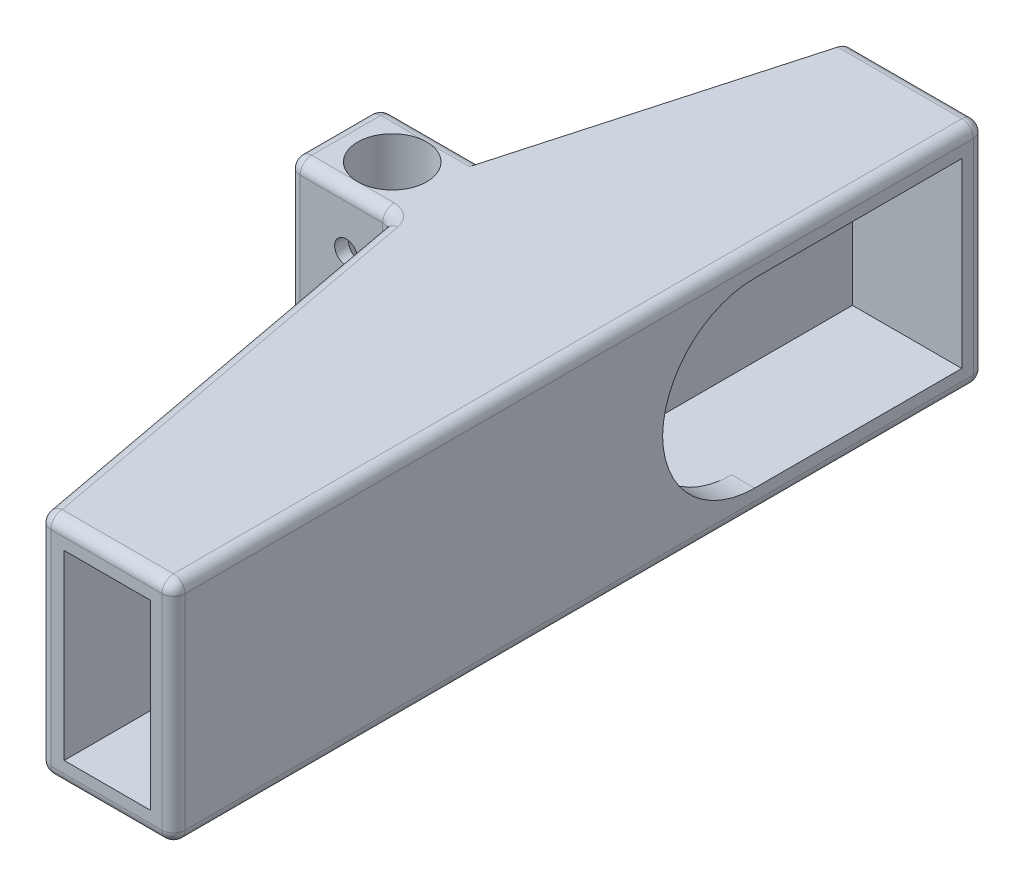
SolidWorks part; units mm, degrees
ref_plane "Alzado" through (0, 0, 0) normal (1, 0, 0) x (0, 1, 0)
ref_plane "Planta" through (0, 0, 0) normal (0, 0, 1) x (0, 1, 0)
ref_plane "Vista lateral" through (0, 0, 0) normal (0, 1, 0) x (-1, 0, 0)
sketch "Croquis1" plane through (0, 0, 0) normal (0, 0, 1) x (0, 1, 0)
  line L1 (-9.9, -5.75) -> (9.9, -5.75)
  line L2 (-9.9, -5.75) -> (-9.9, 5.75)
  line L3 (-9.9, 5.75) -> (9.9, 5.75)
  line L4 (9.9, -5.75) -> (9.9, 5.75)
  line L5 (-9.9, -5.75) -> (9.9, 5.75) construction
  line L6 (-9.9, 5.75) -> (9.9, -5.75) construction
  point P0 (0, 0)
  dimension "D1" = 19.8
  dimension "D2" = 11.5
extrude "Saliente-Extruir1" add sketch "Croquis1" along normal blind 70.5 contours L2 L1 L4 L3
shell "Vaciado1" thickness 2 removed face at (0, 0, 70.5)
sketch "Croquis4" plane through (5.75, 0, 0) normal (1, 0, 0) x (0, 1, 0)
sketch "Croquis5" plane through (5.75, 0, 0) normal (1, 0, 0) x (0, 1, 0)
  line L0 (-7.9, 70.5) -> (-7.9, 68.5)
  line L1 (-7.9, 70.5) -> (7.9, 70.5)
  line L2 (-7.9, 68.5) -> (7.9, 68.5)
  line L3 (7.9, 70.5) -> (7.9, 68.5)
  line L5 (-9.9, 70.5) -> (9.9, 70.5) construction
  point P0 (0, 0)
  dimension "D1" = 15.8
  dimension "D2" = 2
extrude "Saliente-Extruir2" add sketch "Croquis5" against normal blind 2 contours L0 L1 L3 L2
sketch "Croquis6" plane through (-5.75, 0, 0) normal (-1, 0, 0) x (0, -1, 0)
  line L0 (-9.9, 25) -> (9.9, 25)
  line L1 (-9.9, 25) -> (-9.9, 33)
  line L2 (9.9, 25) -> (9.9, 33)
  line L3 (-9.9, 33) -> (9.9, 33)
  line L4 (9.9, 0) -> (-9.9, 0) construction
  line L5 (-9.9, 70.5) -> (-9.9, 0) construction
  line L6 (9.9, 70.5) -> (9.9, 0) construction
  dimension "D1" = 8
  dimension "D2" = 25
extrude "Saliente-Extruir4" add sketch "Croquis6" along normal blind 16
sketch "Croquis9" plane through (0, -9.9, 0) normal (0, -1, 0) x (1, 0, 0)
  line L0 (-5.75, 70.5) -> (-12.75, 33)
  line L1 (-21.75, 33) -> (-5.75, 33) construction
  line L2 (-12.75, 33) -> (-5.75, 33)
  line L3 (-5.75, 33) -> (-5.75, 70.5)
  line L4 (-5.75, 0) -> (-12.75, 25)
  line L5 (-21.75, 25) -> (-5.75, 25) construction
  line L6 (-12.75, 25) -> (-5.75, 25)
  line L7 (-5.75, 25) -> (-5.75, 0) construction
  line L8 (-5.75, 25) -> (-5.75, 0)
  dimension "D1" = 7
  dimension "D2" = 7
extrude "Saliente-Extruir5" add sketch "Croquis9" against normal blind 19.8
sketch "Croquis10" plane through (0, -9.9, 0) normal (0, -1, 0) x (1, 0, 0)
  line L0 (-21.75, 25) -> (-21.75, 33) construction
  circle A0 centre (-16.7453, 29) radius 3
  point P4 (-21.75, 29)
  dimension "D1" = 6
  dimension "D2" = 5.0047
extrude "Cortar-Extruir4" cut sketch "Croquis10" against normal blind 19.8
sketch "Croquis8" plane through (-4, 0, 33) normal (0, 0, 1) x (1, 0, 0)
  line L0 (-17.75, -9.9) -> (-8.75, -9.9) construction
  line L1 (-17.75, -9.9) -> (-17.75, 9.9) construction
  circle A0 centre (-12.75, 5.1) radius 1
  circle A1 centre (-12.75, -4.9) radius 1
  point P0 (0, 0)
  dimension "D4" = 2
  dimension "D5" = 2
  dimension "D1" = 10
  dimension "D2" = 5
  dimension "D3" = 5
extrude "Cortar-Extruir3" cut sketch "Croquis8" against normal through all both and the other way through all contours A0 | A1 | A0 region at (-16.75, 5.1, 33)
sketch "Croquis11" plane through (5.75, 0, 0) normal (1, 0, 0) x (0, 1, 0)
  line L2 (-7.9, 2) -> (7.9, 2)
  line L6 (7.9, 2) -> (7.9, 28)
  line L7 (-7.9, 2) -> (-7.9, 28)
  line L8 (-7.9, 28) -> (7.9, 28)
extrude "Cortar-Extruir5" cut sketch "Croquis11" against normal blind 2
fillet "Redondeo2" radius 8 2 edges at (4.75, -7.9, 28) (4.75, 7.9, 28)
fillet "Redondeo4" radius 1 1 edges at (-12.75, 0, 33)
fillet "Redondeo5" radius 1 2 edges at (-5.75, 0, 70.5) (5.75, 0, 70.5)
fillet "Redondeo6" radius 1 14 edges at (5.75, 9.9, 34.75) (5.4571, 9.9, 70.2071) (-17.6653, 9.9, 33) (-12.9417, 9.9, 33.2307) (-9.25, 9.9, 51.75) (-5.5583, 9.9, 70.2693) (5.75, -9.9, 34.75) (5.4571, -9.9, 70.2071) (-17.6653, -9.9, 33) (-12.9417, -9.9, 33.2307) (-9.25, -9.9, 51.75) (-5.5583, -9.9, 70.2693) (-0.0847, 9.9, 70.5) (-0.0847, -9.9, 70.5)
fillet "Redondeo7" radius 1 6 edges at (-21.75, 0, 25) (5.4571, 9.6071, 0) (5.4571, -9.6071, 0) (5.75, 0, 0) (-0.5, -9.9, 0) (-0.5, 9.9, 0)
fillet "Redondeo8" radius 1 9 edges at (-21.75, 9.9, 29) (-21.75, 9.6071, 32.7071) (-21.75, -9.9, 29) (-21.75, -9.6071, 32.7071) (-21.75, 0, 33) (-16.75, -9.9, 25) (-21.4571, -9.9, 25.2929) (-16.75, 9.9, 25) (-21.4571, 9.9, 25.2929)
equation "\"15.8mm.\"=19.8"
